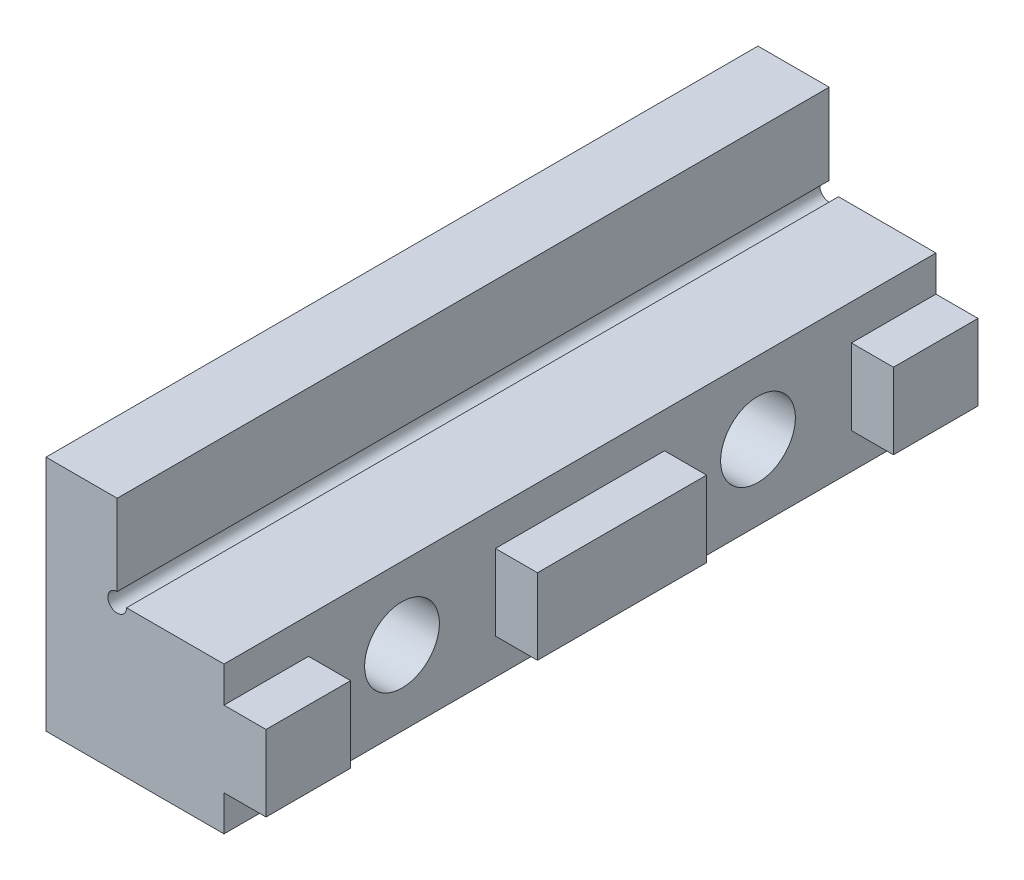
SolidWorks part; units mm, degrees
ref_plane "Front Plane" through (0, 0, 0) normal (0, 0, 1) x (1, 0, 0)
ref_plane "Top Plane" through (0, 0, 0) normal (0, 1, 0) x (1, 0, 0)
ref_plane "Right Plane" through (0, 0, 0) normal (1, 0, 0) x (0, 0, -1)
sketch "Sketch1" plane through (0, 0, 0) normal (0, 0, 1) x (1, 0, 0)
  line L0 (0, 0) -> (0, 25.4)
  line L1 (0, 25.4) -> (7.62, 25.4)
  line L2 (7.62, 25.4) -> (7.62, 16.748)
  line L3 (8.62, 15.748) -> (19.05, 15.748)
  line L4 (19.05, 15.748) -> (19.05, 0)
  line L5 (19.05, 0) -> (0, 0)
  line L6 (7.62, 16.748) -> (7.62, 15.748) construction
  line L7 (7.62, 15.748) -> (8.62, 15.748) construction
  line L8 (19.05, 11.934) -> (23.55, 11.934)
  line L9 (23.55, 11.934) -> (23.55, 3.814)
  line L10 (23.55, 3.814) -> (19.05, 3.814)
  line L11 (19.05, 7.874) -> (23.55, 7.874) construction
  arc A0 (7.62, 16.748) -> (8.62, 15.748) centre (7.62, 15.748) ccw
  dimension "D4" = 2
  dimension "D1" = 19.05
  dimension "D2" = 7.62
  dimension "D3" = 25.4
  dimension "D5" = 9.652
  dimension "D6" = 8.12
  dimension "D7" = 4.5
extrude "Boss-Extrude1" add sketch "Sketch1" against normal blind 38.1 and the other way blind 38.1 contours A0 L2 L1 L0 L5 L4 L3 | L10 L9 L8 L4 region at (8.4056, 10.3413, 0) region at (21.3, 7.874, 0)
sketch "Sketch2" plane through (0, 0, 0) normal (1, 0, 0) x (0, 0, -1)
  line L0 (-19.05, 8) -> (19.05, 8) construction
  line L3 (0, 0) -> (0, 8) construction
  circle A0 centre (-19.05, 8) radius 4
  circle A1 centre (19.05, 8) radius 4
  dimension "D4" = 8
  dimension "D1" = 8
  dimension "D3" = 38.1
extrude "Cut-Extrude1" cut sketch "Sketch2" along normal blind 55.4
sketch "Sketch3" plane through (0, 0, 0) normal (1, 0, 0) x (0, 0, -1)
  circle A0 centre (-19.05, 8) radius 6.5
  circle A1 centre (19.05, 8) radius 6.5
  dimension "D1" = 13
extrude "Cut-Extrude2" cut sketch "Sketch3" along normal blind 8.2
sketch "Sketch4" plane through (0, 0, 0) normal (1, 0, 0) x (0, 0, -1)
  line L0 (-19.05, 8) -> (19.05, 8) construction
  line L1 (0, 0) -> (0, 8) construction
  line L3 (-29.05, 0.5) -> (-9.05, 0.5)
  line L4 (-29.05, 0.5) -> (-29.05, 15.5)
  line L5 (-29.05, 15.5) -> (-9.05, 15.5)
  line L6 (-9.05, 0.5) -> (-9.05, 15.5)
  line L7 (-29.05, 0.5) -> (-9.05, 15.5) construction
  line L8 (-29.05, 15.5) -> (-9.05, 0.5) construction
  line L9 (9.05, 15.5) -> (29.05, 15.5)
  line L10 (9.05, 15.5) -> (9.05, 0.5)
  line L11 (9.05, 0.5) -> (29.05, 0.5)
  line L12 (29.05, 15.5) -> (29.05, 0.5)
  line L13 (9.05, 15.5) -> (29.05, 0.5) construction
  line L14 (9.05, 0.5) -> (29.05, 15.5) construction
  dimension "D1" = 20
  dimension "D2" = 20
  dimension "D3" = 15
  dimension "D4" = 15
extrude "Cut-Extrude3" cut sketch "Sketch4" along normal blind 10 from surface starting at face at (19.05, 12.904, 0)
